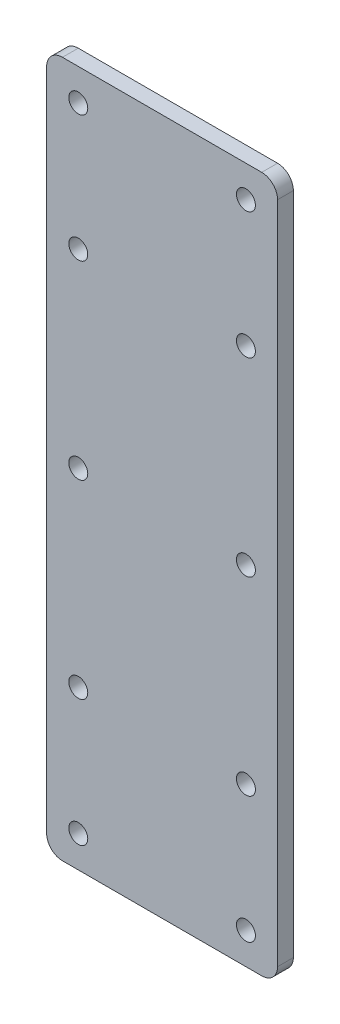
SolidWorks part; units mm, degrees
material "6061 Alloy"
ref_plane "Front Plane" through (0, 0, 0) normal (0, 0, 1) x (1, 0, 0)
ref_plane "Top Plane" through (0, 0, 0) normal (0, 1, 0) x (1, 0, 0)
ref_plane "Right Plane" through (0, 0, 0) normal (1, 0, 0) x (0, 0, -1)
sketch "Sketch2" plane through (0, 0, 0) normal (0, 0, 1) x (1, 0, 0)
  line L0 (36.5, 220) -> (36.5, 0) construction
  line L1 (5, 0) -> (68, 0)
  line L2 (0, 5) -> (0, 215)
  line L3 (5, 220) -> (68, 220)
  line L4 (73, 5) -> (73, 215)
  line L5 (10, 210) -> (63, 210)
  line L6 (10, 210) -> (10, 170)
  line L7 (10, 170) -> (63, 170)
  line L8 (63, 210) -> (63, 170)
  line L9 (0, 110) -> (73, 110) construction
  line L10 (10, 50) -> (63, 50)
  line L11 (10, 50) -> (10, 10)
  line L12 (10, 10) -> (63, 10)
  line L13 (63, 50) -> (63, 10)
  circle A0 centre (10, 210) radius 3
  circle A1 centre (63, 210) radius 3
  circle A2 centre (63, 170) radius 3
  circle A3 centre (10, 170) radius 3
  circle A4 centre (63, 50) radius 3
  circle A5 centre (10, 50) radius 3
  circle A6 centre (10, 10) radius 3
  circle A7 centre (63, 10) radius 3
  circle A8 centre (10, 110) radius 3
  circle A9 centre (63, 110) radius 3
  arc A10 (5, 0) -> (0, 5) centre (5, 5) cw
  arc A11 (68, 0) -> (73, 5) centre (68, 5) ccw
  arc A12 (68, 220) -> (73, 215) centre (68, 215) cw
  arc A13 (0, 215) -> (5, 220) centre (5, 215) cw
  point P11 (36.5, 210)
  point P20 (36.5, 10)
  point P34 (0, 0)
  dimension "D5" = 6
  dimension "D8" = 5
  dimension "D1" = 53
  dimension "D2" = 40
  dimension "D3" = 10
  dimension "D4" = 10
  dimension "D6" = 120
  dimension "D7" = 10
extrude "Boss-Extrude1" add sketch "Sketch2" along normal blind 5 contours A13 L2 A10 L1 A11 L4 A12 L3 A9 A8 A7 L12 A6 L11 A5 L10 A4 L13 A3 L6 A0 L5 A1 L8 A2 L7 | A3 L7 A2 L8 A1 L5 A0 L6 | A7 L13 A4 L10 A5 L11 A6 L12 region at (36.5, 110, 0) region at (36.5, 190, 0) region at (36.5, 30, 0)
